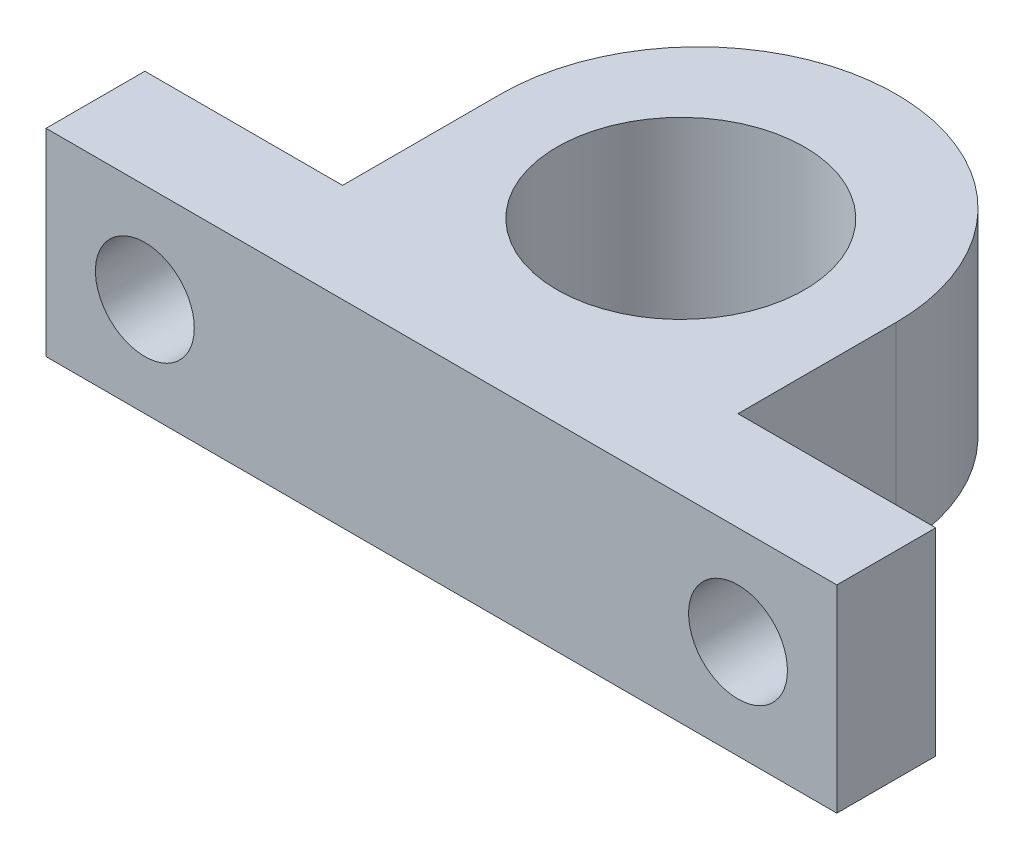
SolidWorks part; units mm, degrees
ref_plane "Front Plane" through (0, 0, 0) normal (0, 0, 1) x (1, 0, 0)
ref_plane "Top Plane" through (0, 0, 0) normal (0, 1, 0) x (1, 0, 0)
ref_plane "Right Plane" through (0, 0, 0) normal (1, 0, 0) x (0, 0, -1)
sketch "Sketch1" plane through (0, 0, 0) normal (0, 1, 0) x (1, 0, 0)
  line L0 (-25.4, 0) -> (25.4, 0)
  line L2 (0, -55) -> (0, 55) construction
  line L4 (-25.4, 0) -> (-25.4, 6.35)
  line L5 (-25.4, 6.35) -> (-12.7, 6.35)
  line L6 (-12.7, 6.35) -> (-12.7, 16.51)
  line L7 (12.7, 6.35) -> (12.7, 16.51)
  line L8 (25.4, 6.35) -> (12.7, 6.35)
  line L9 (25.4, 0) -> (25.4, 6.35)
  arc A0 (-12.7, 16.51) -> (12.7, 16.51) centre (0, 16.51) cw
  point P3 (6.281, 6.35)
  point P4 (0, 0)
  point P14 (-6.281, 6.35)
  point P15 (-25.4302, 0)
  point P16 (-6.35, 23.3601)
  point P17 (-6.35, 6.35)
  point P18 (-6.35, 6.35)
  point P19 (-6.35, 17.8131)
  point P20 (-12.2477, 17.8131)
  point P21 (-11.6087, 6.35)
  point P22 (-12.7, 8.4582)
  point P23 (-12.7, 13.3526)
  dimension "D2" = 12.7
  dimension "D5" = 25.4
  dimension "D1" = 50.8
  dimension "D3" = 6.35
  dimension "D4" = 10.16
extrude "Boss-Extrude1" add sketch "Sketch1" along normal blind 12.7
sketch "Sketch2" plane through (0, 12.7, 0) normal (0, 1, 0) x (1, 0, 0)
  circle A0 centre (0, 15.3754) radius 7.9502
  point P2 (0.1541, 9.9292)
  point P3 (0, 0)
  point P5 (0, 9.0304)
  point P6 (0, 12.8611)
  point P7 (0, 15.3754)
  dimension "D1" = 15.9004
extrude "Cut-Extrude1" cut sketch "Sketch2" against normal through all contours A0
sketch "Sketch3" plane through (0, 0, 0) normal (0, 0, 1) x (1, 0, 0)
  line L0 (-25.4, 0) -> (25.4, 0) construction
  line L2 (0, -6.985) -> (0, 6.985) construction
  line L3 (-25.4, 12.7) -> (-25.4, 0) construction
  circle A0 centre (-19.05, 6.35) radius 3.175
  circle A1 centre (19.05, 6.35) radius 3.175
  dimension "D1" = 6.35
  dimension "D2" = 6.35
extrude "Cut-Extrude2" cut sketch "Sketch3" against normal through all contours A0 | A1
